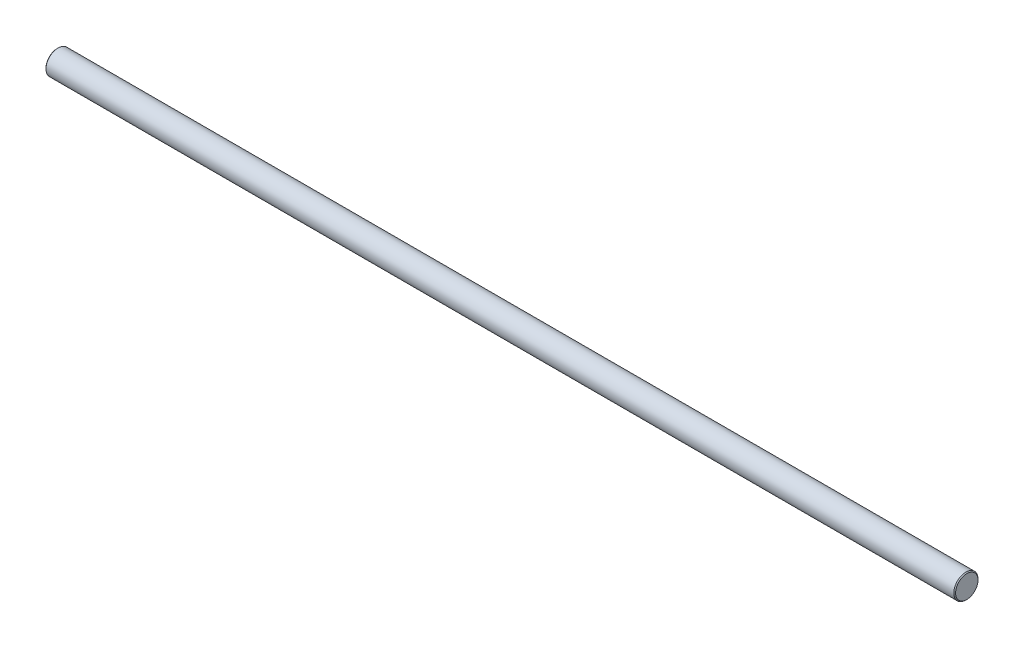
SolidWorks part; units mm, degrees
material "SUJ2"
ref_plane "Front Plane" through (0, 0, 0) normal (0, 0, 1) x (1, 0, 0)
ref_plane "Top Plane" through (0, 0, 0) normal (0, 1, 0) x (1, 0, 0)
ref_plane "Right Plane" through (0, 0, 0) normal (1, 0, 0) x (0, 0, -1)
sketch "Sketch1" plane through (0, 0, 0) normal (0, 0, 1) x (1, 0, 0)
  line L0 (0, 0) -> (300, 0) construction
  line L2 (0, 0) -> (300, 0)
  line L3 (0, 0) -> (0, 4)
  line L4 (0, 4) -> (300, 4)
  line L5 (300, 0) -> (300, 4)
  dimension "D" = 8
  dimension "L" = 300
revolve "Revolve1" add sketch "Sketch1" angle 360 about L0
chamfer "Chamfer1" distance 0.3 angle 45 2 edges at (300, 0, 4) (0, 0, 4)
sketch "Sketch2" plane through (0, 0, 0) normal (0, 0, 1) x (1, 0, 0)
  line L0 (0, 0) -> (300, 0) construction
  line L1 (300, 0) -> (300, 4) construction
  line L2 (0, 0) -> (300, 0)
  line L3 (0, 0) -> (0, 1.25)
  line L4 (0, 1.25) -> (300, 1.25)
  line L5 (300, 0) -> (300, 1.25)
  dimension "D_s" = 2.5
revolve "Cut-Revolve1" [suppressed] cut sketch "Sketch2" angle 360 about L0
